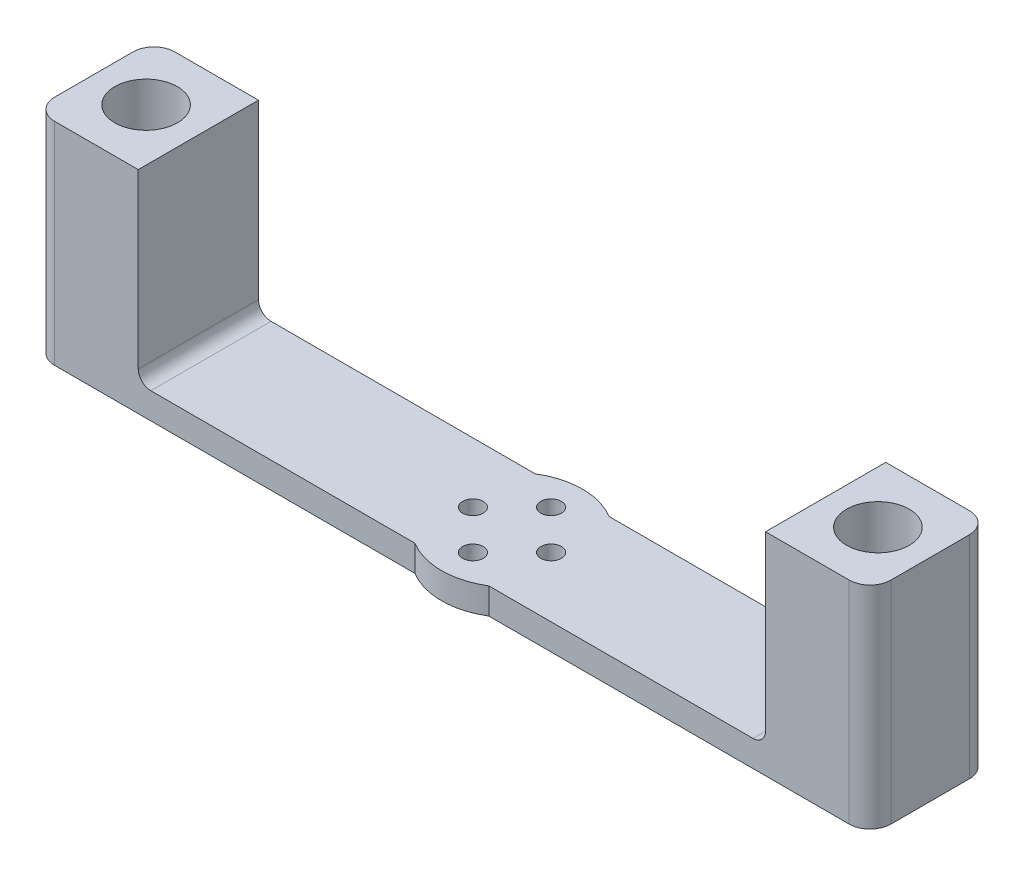
SolidWorks part; units mm, degrees
ref_plane "Front Plane" through (0, 0, 0) normal (0, 0, 1) x (1, 0, 0)
ref_plane "Top Plane" through (0, 0, 0) normal (0, 1, 0) x (1, 0, 0)
ref_plane "Right Plane" through (0, 0, 0) normal (1, 0, 0) x (0, 0, -1)
sketch "Sketch1" plane through (0, 0, 0) normal (0, 1, 0) x (1, 0, 0)
  line L0 (0, 0) -> (0, 4.9523) construction
  line L1 (0, 4.9523) -> (0, 0) construction
  line L2 (0, 0) -> (2.8355, 0) construction
  circle A0 centre (0, 0) radius 17.145
  circle A2 centre (0, 9.5) radius 2.5
  circle A3 centre (9.5, 0) radius 2.5
  circle A4 centre (0, -9.5) radius 2.5
  circle A5 centre (-9.5, 0) radius 2.5
  dimension "D2" = 34.29
  dimension "D3" = 5
extrude "Boss-Extrude1" add sketch "Sketch1" along normal blind 6.35
sketch "Sketch2" plane through (0, 6.35, 0) normal (0, 1, 0) x (1, 0, 0)
  line L1 (-96.52, -14.605) -> (96.52, -14.605)
  line L2 (-101.6, -9.525) -> (-101.6, 9.525)
  line L3 (-96.52, 14.605) -> (96.52, 14.605)
  line L4 (101.6, -9.525) -> (101.6, 9.525)
  line L5 (-101.6, -14.605) -> (101.6, 14.605) construction
  line L6 (-101.6, 14.605) -> (101.6, -14.605) construction
  circle A0 centre (-88.9, 0) radius 7.62
  circle A1 centre (88.9, 0) radius 7.62
  arc A3 (96.52, 14.605) -> (101.6, 9.525) centre (96.52, 9.525) cw
  arc A4 (96.52, -14.605) -> (101.6, -9.525) centre (96.52, -9.525) ccw
  arc A5 (-96.52, -14.605) -> (-101.6, -9.525) centre (-96.52, -9.525) cw
  arc A6 (-101.6, 9.525) -> (-96.52, 14.605) centre (-96.52, 9.525) cw
  circle A7 centre (9.5, 0) radius 2.5 construction
  circle A8 centre (0, 9.5) radius 2.5 construction
  circle A9 centre (-9.5, 0) radius 2.5 construction
  circle A10 centre (0, -9.5) radius 2.5 construction
  circle A11 centre (9.5, 0) radius 2.5
  circle A12 centre (0, 9.5) radius 2.5
  circle A13 centre (-9.5, 0) radius 2.5
  circle A14 centre (0, -9.5) radius 2.5
  point P0 (0, 0)
  dimension "D2" = 15.24
  dimension "D3" = 15.24
  dimension "D8" = 5.08
  dimension "D1" = 29.21
  dimension "D4" = 88.9
  dimension "D6" = 12.7
  dimension "D7" = 12.7
extrude "Boss-Extrude2" add sketch "Sketch2" along normal blind 45 and the other way through all
sketch "Sketch5" plane through (0, 0, -14.605) normal (0, 0, -1) x (-1, 0, 0)
  line L0 (-101.6, 0) -> (-101.6, 51.35)
  line L1 (-101.6, 51.35) -> (-76.2, 51.35)
  line L2 (-96.52, 51.35) -> (96.52, 51.35) construction
  line L3 (-76.2, 51.35) -> (-76.2, 6.35)
  line L4 (-76.2, 6.35) -> (76.2, 6.35)
  line L5 (0, 6.35) -> (0, 0)
  line L6 (101.6, 0) -> (-101.6, 0)
  line L7 (76.2, 51.35) -> (76.2, 6.35)
  line L8 (101.6, 51.35) -> (76.2, 51.35)
  line L9 (101.6, 0) -> (101.6, 51.35)
  line M8 (96.52, 51.35) -> (-96.52, 51.35)
  dimension "D1" = 25.4
  dimension "D2" = 6.35
extrude "Cut-Extrude2" cut sketch "Sketch5" against normal through all contours L7 L3 L4 M8 region at (0, 28.85, -14.605)
sketch "Sketch6" plane through (0, 0, 0) normal (0, -1, 0) x (1, 0, 0)
  circle A0 centre (-88.9, 0) radius 8.89
  circle A1 centre (-88.9, 0) radius 4.445
  circle A2 centre (88.9, 0) radius 8.89
  circle A3 centre (88.9, 0) radius 4.445
  dimension "D1" = 8.89
  dimension "D2" = 8.89
extrude "Boss-Extrude3" add sketch "Sketch6" against normal blind 4.572
fillet "Fillet2" radius 3.048 2 edges at (76.2, 6.35, 0) (-76.2, 6.35, 0)
